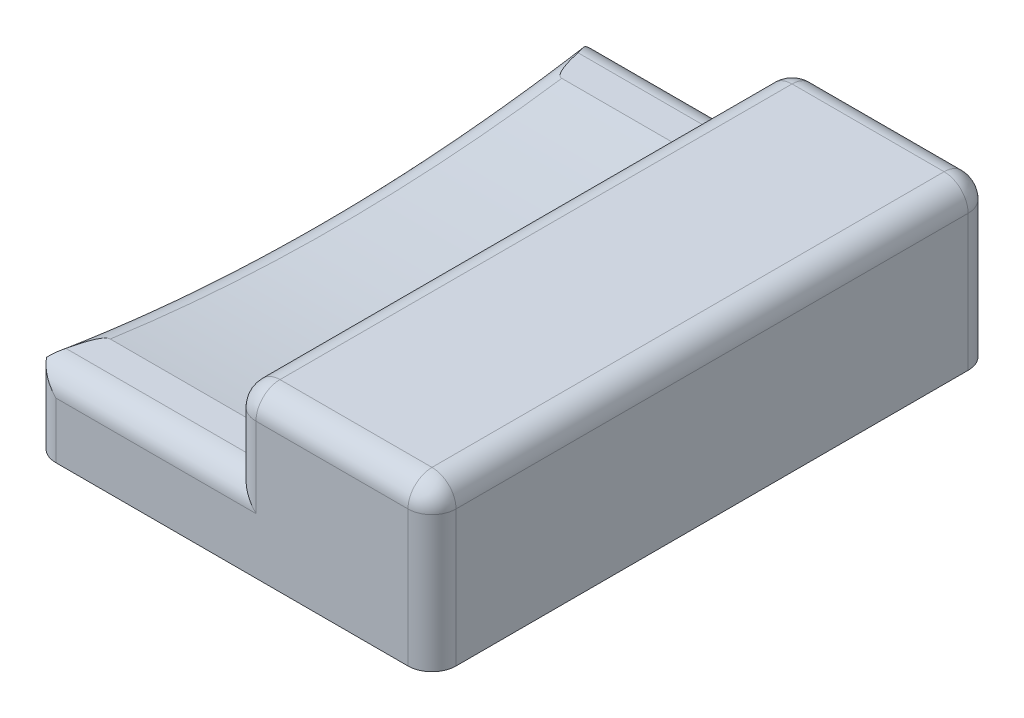
SolidWorks part; units mm, degrees
ref_plane "Front Plane" through (0, 0, 0) normal (0, 0, 1) x (1, 0, 0)
ref_plane "Top Plane" through (0, 0, 0) normal (0, 1, 0) x (1, 0, 0)
ref_plane "Right Plane" through (0, 0, 0) normal (1, 0, 0) x (0, 0, -1)
sketch "Sketch1" plane through (0, 0, 0) normal (0, 1, 0) x (1, 0, 0)
  line L1 (0, 0) -> (50, 0)
  line L2 (0, 0) -> (0, 70)
  line L3 (0, 70) -> (50, 70)
  line L4 (50, 0) -> (50, 70)
  dimension "D1" = 70
  dimension "D2" = 50
extrude "Boss-Extrude1" add sketch "Sketch1" along normal blind 20
sketch "Sketch3" plane through (0, 0, 0) normal (-1, 0, 0) x (0, 0, 1)
  line L0 (0, 20) -> (0, 0) construction
  line L1 (-70, 20) -> (0, 20)
  line L2 (-70, 20) -> (-70, 10)
  line L3 (-70, 10) -> (-63.2135, 10)
  line L4 (0, 20) -> (0, 10)
  line L5 (-6.7865, 10) -> (0, 10)
  arc A0 (-63.2135, 10) -> (-6.7865, 10) centre (-35, 208) ccw
  dimension "D1" = 400
  dimension "D2" = 198
extrude "Cut-Extrude1" cut sketch "Sketch3" against normal blind 25
fillet "Fillet1" radius 3 13 edges at (25, 15, -70) (25, 15, 0) (12.5, 10, -70) (0, 8, -35) (12.5, 10, 0) (37.5, 20, -70) (50, 20, -35) (37.5, 20, 0) (25, 20, -35) (0, 5, 0) (0, 5, -70) (50, 10, -70) (50, 10, 0)
